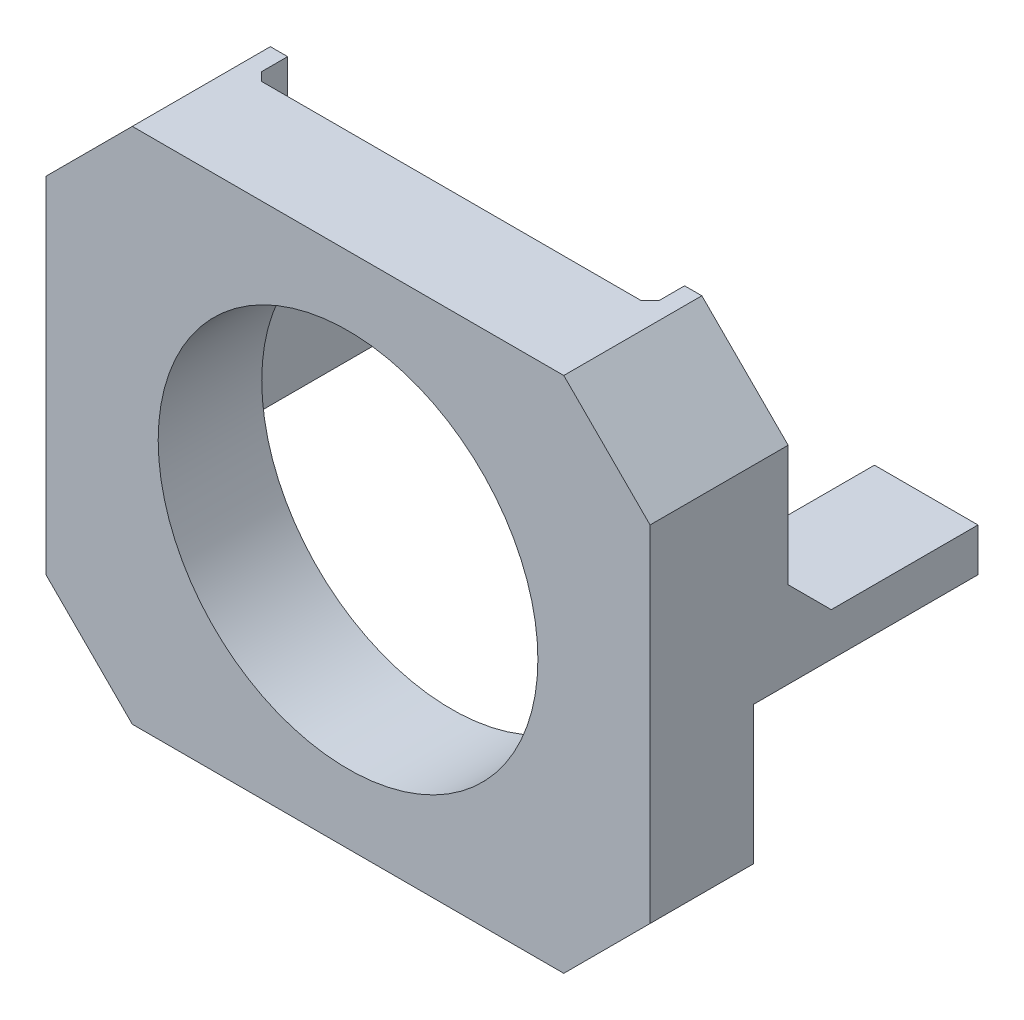
SolidWorks part; units mm, degrees
ref_plane "Front Plane" through (0, 0, 0) normal (0, 0, 1) x (1, 0, 0)
ref_plane "Top Plane" through (0, 0, 0) normal (0, 1, 0) x (1, 0, 0)
ref_plane "Right Plane" through (0, 0, 0) normal (1, 0, 0) x (0, 0, -1)
sketch "Sketch1" plane through (0, 0, 0) normal (0, 0, 1) x (1, 0, 0)
  line L1 (-17.5, 15) -> (17.5, 15)
  line L2 (-17.5, 15) -> (-17.5, -15)
  line L3 (-17.5, -15) -> (17.5, -15)
  line L4 (17.5, 15) -> (17.5, -15)
  line L5 (-17.5, 15) -> (17.5, -15) construction
  line L6 (-17.5, -15) -> (17.5, 15) construction
  circle A0 centre (0, 0) radius 11
  dimension "D1" = 22
  dimension "D2" = 30
  dimension "D3" = 35
extrude "Boss-Extrude1" add sketch "Sketch1" along normal blind 6
sketch "Sketch2" plane through (0, 0, 0) normal (0, 0, -1) x (-1, 0, 0)
  line L1 (-17.5, 15) -> (-11.5, 15)
  line L2 (-17.5, 15) -> (-17.5, -2)
  line L3 (-17.5, -2) -> (-11.5, -2)
  line L4 (-11.5, 15) -> (-11.5, -2)
  line L5 (17.5, 15) -> (11.5, 15)
  line L6 (17.5, 15) -> (17.5, -2)
  line L7 (17.5, -2) -> (11.5, -2)
  line L8 (11.5, 15) -> (11.5, -2)
  line M11 (17.5, -15) -> (17.5, 15)
  line M12 (17.5, 15) -> (-17.5, 15)
  dimension "D1" = 2
  dimension "D2" = 6
extrude "Boss-Extrude2" add sketch "Sketch2" along normal blind 2 contours L8 L7 M12 M11 | L2 L1 L4 L3 region at (-14.5, 6.5, 0)
sketch "Sketch3" plane through (0, 0, -2) normal (0, 0, -1) x (-1, 0, 0)
  line L0 (-11.5, 15) -> (-11.5, -2) construction
  line L1 (-17.5, -2) -> (-11.5, -2)
  line L2 (-17.5, -2) -> (-17.5, 0.5)
  line L3 (-17.5, 0.5) -> (-11.5, 0.5)
  line L4 (-11.5, -2) -> (-11.5, 0.5)
  line L5 (0, 0) -> (0, -50000) construction
  line L6 (17.5, 0.5) -> (11.5, 0.5)
  line L7 (11.5, -2) -> (11.5, 0.5)
  line L8 (17.5, -2) -> (11.5, -2)
  line L9 (17.5, -2) -> (17.5, 0.5)
  dimension "D1" = 2.5
extrude "Boss-Extrude3" add sketch "Sketch3" along normal blind 11 contours L8 L9 L6 L7 | L2 L1 L4 L3 region at (-14.5, -0.75, -2)
chamfer "Chamfer1" distance 5 4 edges at (17.5, -15, 3) (-17.5, -15, 3) (-17.5, 15, 2) (17.5, 15, 2)
chamfer "Chamfer2" distance 2.5 2 edges at (-14.5, 0.5, -2) (14.5, 0.5, -2)
chamfer "Chamfer3" distance 0.5 2 edges at (-11.5, 6.5, 0) (11.5, 6.5, 0)
